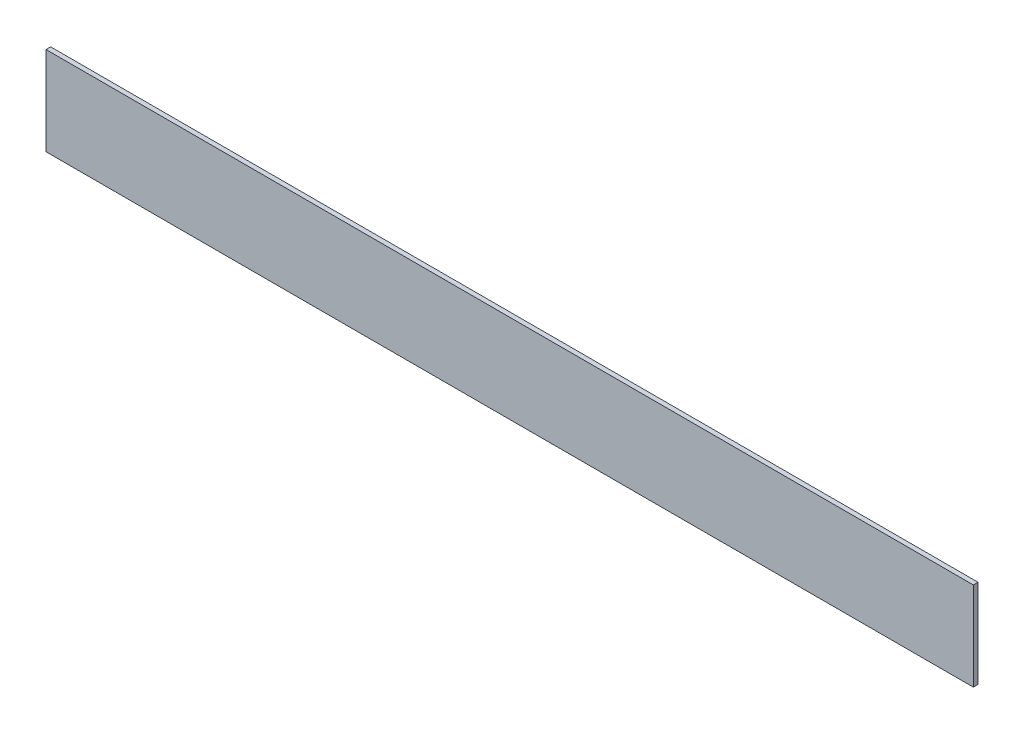
SolidWorks part; units mm, degrees
ref_plane "Ön Düzlem" through (0, 0, 0) normal (0, 0, 1) x (1, 0, 0)
ref_plane "Üst Düzlem" through (0, 0, 0) normal (0, 1, 0) x (1, 0, 0)
ref_plane "Sağ Düzlem" through (0, 0, 0) normal (1, 0, 0) x (0, 0, -1)
sketch "Çizim1" plane through (0, 0, 0) normal (0, 0, 1) x (1, 0, 0)
  line L1 (0, 0) -> (995, 0)
  line L2 (0, 0) -> (0, -95)
  line L3 (0, -95) -> (995, -95)
  line L4 (995, 0) -> (995, -95)
  dimension "D1" = 995
  dimension "D2" = 95
base flange "Taban-Flanş1" sketch "Çizim1" thickness 5 reverse thickness direction no parameters "D1"=6
sketch "Büküm-Çizgileri1" [suppressed] plane through (0, 0, 0) normal (0, 1, 0) x (1, 0, 0)
sketch "Sınırlandırma-Kutusu1" [suppressed] plane through (0, 0, 0) normal (0, 1, 0) x (1, 0, 0)
sheet metal parameters "Sac-Levha1" thickness 5 parameters "D1"=6
flat pattern "Düz-Çoğaltma1" [suppressed]
sketch "Büküm-Çizgileri2" plane through (0, 0, 0) normal (0, 1, 0) x (1, 0, 0)
sketch3d "Sınırlandırma-Kutusu2" [suppressed]
  line L0 (0, -95, 0) -> (995, -95, 0) construction
  line L1 (0, 0, 0) -> (995, 0, 0) construction
  line L2 (0, -95, 0) -> (0, 0, 0) construction
  line L3 (995, -95, 0) -> (995, 0, 0) construction
